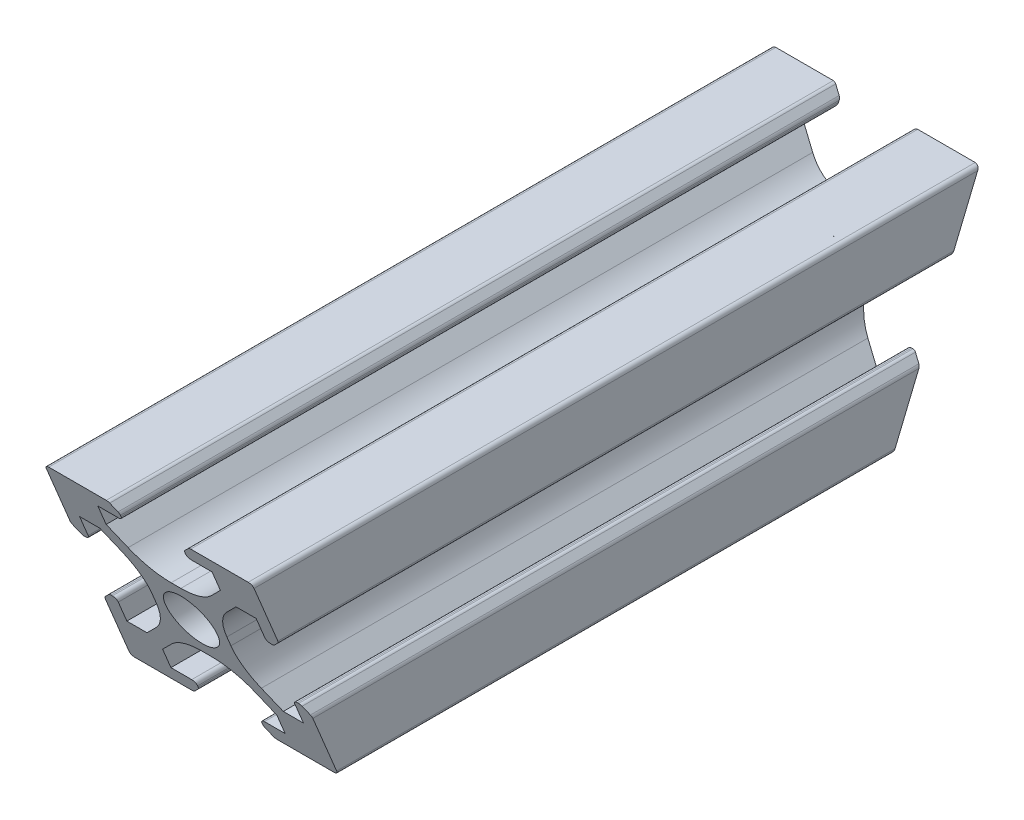
SolidWorks part; units mm, degrees
material "6063-O"
ref_plane "Plano frontal" through (0, 0, 0) normal (0, 0, 1) x (1, 0, 0)
ref_plane "Plano superior" through (0, 0, 0) normal (0, 1, 0) x (1, 0, 0)
ref_plane "Plano direito" through (0, 0, 0) normal (1, 0, 0) x (0, 0, -1)
sketch "Esboço1" plane through (0, 0, 0) normal (0, 0, 1) x (1, 0, 0)
  line L0 (-9.0343, 3.1) -> (-8.9, 3.1)
  line L3 (-10, 10) -> (-4.0657, 10)
  line L5 (-10, -10) -> (10, 10) construction
  line L6 (-10, 10) -> (10, -10) construction
  line L7 (-8.5, 3.5) -> (-8.5, 5.5)
  line L8 (-10, 0) -> (10, 0) construction
  line L9 (0, 10) -> (0, -10) construction
  line L12 (-8.5, 5.5) -> (-6.5607, 5.5)
  line L15 (-6.5607, 5.5) -> (-5.0645, 4.0038)
  line L16 (-3.6, 0.4683) -> (-3.6, 0)
  line L17 (-0.4683, 3.6) -> (0, 3.6)
  line L18 (-5.5, 6.5607) -> (-4.0038, 5.0645)
  line L21 (-5.5, 8.5) -> (-5.5, 6.5607)
  line L24 (-3.5, 8.5) -> (-5.5, 8.5)
  line L25 (-3.1, 9.0343) -> (-3.1, 8.9)
  line L44 (-10, 4.0657) -> (-10, 10)
  line L45 (-9.8828, 3.7828) -> (-9.3172, 3.2172)
  line L46 (-3.7828, 9.8828) -> (-3.2172, 9.3172)
  line L47 (-3.6, 0) -> (-2.5, 0)
  line L48 (0, 3.6) -> (0, 2.5)
  arc A0 (-3.5, 8.5) -> (-3.1, 8.9) centre (-3.5, 8.9) ccw
  arc A1 (-3.7828, 9.8828) -> (-4.0657, 10) centre (-4.0657, 9.6) ccw
  arc A2 (-10, 4.0657) -> (-9.8828, 3.7828) centre (-9.6, 4.0657) ccw
  arc A3 (-8.5, 3.5) -> (-8.9, 3.1) centre (-8.9, 3.5) cw
  arc A4 (-3.2172, 9.3172) -> (-3.1, 9.0343) centre (-3.5, 9.0343) cw
  arc A5 (-9.3172, 3.2172) -> (-9.0343, 3.1) centre (-9.0343, 3.5) ccw
  arc A6 (-3.6, 0.4683) -> (-5.0645, 4.0038) centre (-8.6, 0.4683) ccw
  arc A7 (-4.0038, 5.0645) -> (-0.4683, 3.6) centre (-0.4683, 8.6) ccw
  circle A8 centre (0, 0) radius 2.5
  point P6 (-10, 3.1)
  point P28 (-3.1, 8.5)
  point P31 (-3.1, 10)
  point P33 (-3.9, 10)
  point P36 (-10, 3.9)
  point P39 (-8.5, 3.1)
  point P42 (-3.1, 9.2)
  point P45 (-9.2, 3.1)
  point P48 (-3.6, 2.5393)
  point P51 (-2.5393, 3.6)
  dimension "D5" = 10
  dimension "D9" = 0.4
  dimension "D10" = 0.4
  dimension "D11" = 5
  dimension "D12" = 5
  dimension "D13" = 5
  dimension "D1" = 6.9
  dimension "D2" = 1.5
  dimension "D3" = 3.6
  dimension "D4" = 1.5
  dimension "D6" = 2.4
  dimension "D7" = 3.6
  dimension "D8" = 45
extrude "Ressalto-extrusão1" add sketch "Esboço1" along normal blind 70 contours A4 A3 L3 A0 L17 L18 L21 L24 L25 L0 L7 L12 L15 L16 region at (-5.9987, 5.9987, 0)
sketch "Esboço3" plane through (0, 0, 0) normal (1, 0, 0) x (0, 0, -1)
  line L0 (0, 0) -> (-70, 0) construction
  line L1 (-70, 2.5) -> (-70, 0) construction
pattern_circular "PadrãoCircular1" count 4 every 90 about axis through (0, 0, 0) along (0, 0, 1) of "Ressalto-extrusão1"
fillet "Filete1" radius 0.4 4 edges at (-10, -10, 35) (-10, 10, 35) (10, -10, 35) (10, 10, 35)
ref_plane "Plane1" through (0, 0, 35) normal (0, 0, 1) x (1, 0, 0)
sketch "Sketch1" plane through (-10, 0, 0) normal (-1, 0, 0) x (0, 0, 1)
  line L0 (0, 10) -> (0, -10)
  line L1 (0, 0) -> (70, 0) construction
  line L2 (0, 10) -> (8.2843, -10)
  line L3 (0, -10) -> (8.2843, -10)
  line L4 (35, 9.6) -> (35, -9.6) construction
  line L5 (70, 9.6) -> (0, 9.6) construction
  line L6 (0, -9.6) -> (70, -9.6) construction
  line L7 (70, 9.6) -> (70, -9.6)
  line L8 (70, -10) -> (61.7157, -10)
  line L9 (70, 10) -> (61.7157, -10)
  line L10 (70, 10) -> (70, -10)
  line M5 (70, 4.0657) -> (70, 9.6)
  line M6 (70, 9.6) -> (0, 9.6)
  line M7 (0, 9.6) -> (0, 4.0657)
  line M8 (0, 4.0657) -> (70, 4.0657)
  dimension "D1" = 10
  dimension "D2" = 22.5
extrude "Cut-Extrude1" cut sketch "Sketch1" against normal through all contours L0 L3 L2 M8 | L2 M6 M7 M8 | L9 M6 M8 M5 | L10 L7 L9 L8 M8 | L10 L9 M6 | L2 L0 M6 region at (-10, 9.7333, 0.0552) region at (-10, 6.027, 0.8228) region at (-10, -4.2386, 2.9489) region at (-10, 6.027, 69.1772) region at (-10, 9.7333, 69.9448) region at (-10, -4.2386, 67.0511)
sketch "Sketch4" plane through (10, 0, 0) normal (1, 0, 0) x (0, 0, -1)
  line L0 (-35, 9.6) -> (-35, -9.6) construction
  line L1 (-0.1657, 9.6) -> (-69.8343, 9.6) construction
  line L2 (-61.8814, -9.6) -> (-8.1186, -9.6) construction
  line L3 (0, 0) -> (-76.6529, 0) construction
  circle A1 centre (-11, 0) radius 1.5
  circle A3 centre (-59, 0) radius 1.5
  dimension "D2" = 3
  dimension "D4" = 11
extrude "Cut-Extrude3" cut sketch "Sketch4" against normal through all
